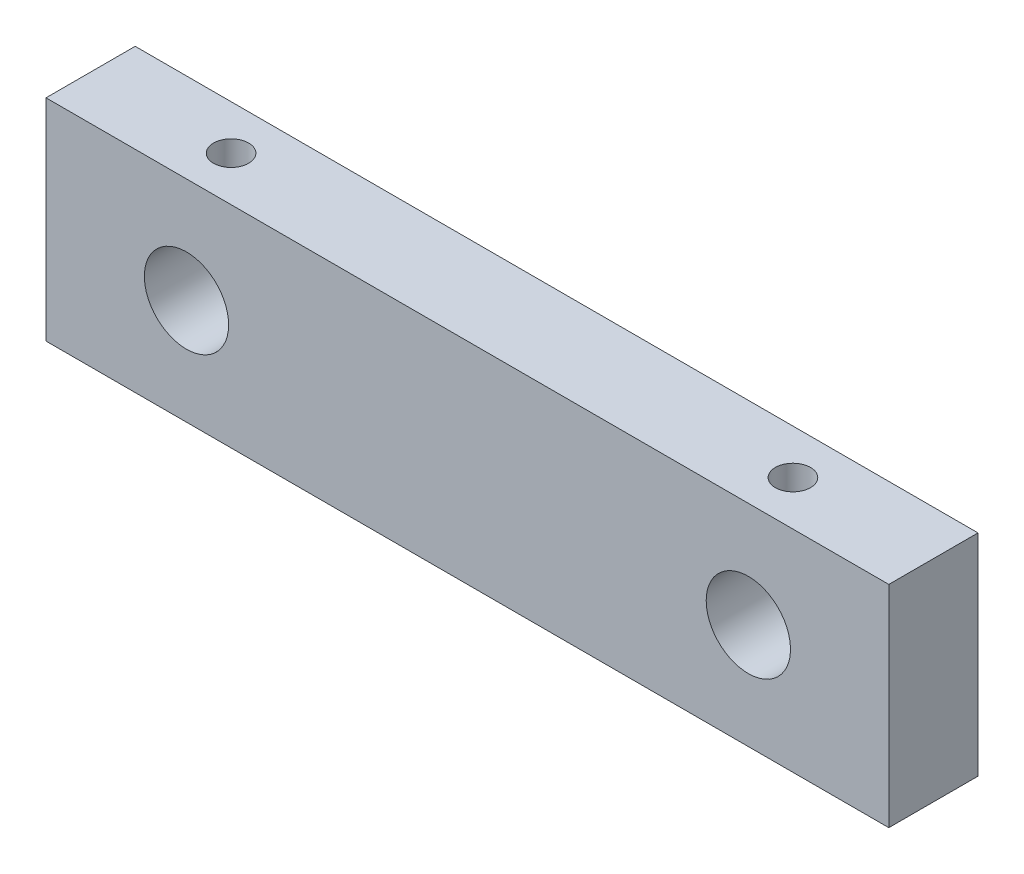
SolidWorks part; units mm, degrees
material "6061 Alloy"
ref_plane "Front Plane" through (0, 0, 0) normal (0, 0, 1) x (1, 0, 0)
ref_plane "Top Plane" through (0, 0, 0) normal (0, 1, 0) x (1, 0, 0)
ref_plane "Right Plane" through (0, 0, 0) normal (1, 0, 0) x (0, 0, -1)
sketch "Sketch1" plane through (0, 0, 0) normal (0, 0, 1) x (1, 0, 0)
  line L0 (30, 15) -> (30, 0) construction
  line L1 (0, 0) -> (60, 0)
  line L2 (0, 0) -> (0, 15)
  line L3 (0, 15) -> (60, 15)
  line L4 (60, 0) -> (60, 15)
  line L5 (0, 7.5) -> (60, 7.5) construction
  circle A0 centre (10, 7.5) radius 3
  circle A1 centre (50, 7.5) radius 3
  dimension "D3" = 6
  dimension "D1" = 60
  dimension "D2" = 15
  dimension "D4" = 40
extrude "Boss-Extrude1" add sketch "Sketch1" along normal blind 6.35
ref_axis "Axis1" through (10, 7.5, 6.35) along (0, 0, -1)
hole_wizard "M3 Tapped Hole1" positions "Sketch4" profile "Sketch3" tap size "M3" standard "ISO"
sketch "Sketch4" plane through (0, 15, 0) normal (0, 1, 0) x (-1, 0, 0)
  line L0 (0, 3.175) -> (-60, 3.175) construction
  line L1 (0, 6.35) -> (0, 0) construction
  line L2 (-60, 6.35) -> (-60, 0) construction
  line L5 (-30, 0) -> (-30, 6.35) construction
  line L6 (-60, 0) -> (0, 0) construction
  line L7 (-60, 6.35) -> (0, 6.35) construction
  line L10 (-10, 6.35) -> (-10, 0) construction
  point P0 (-10, 3.175)
  point P25 (-50, 3.175)
sketch "Sketch3" plane through (10, 15, 3.175) normal (1, 0, 0) x (0, 0, 1)
  line L0 (0, 0) -> (0, 9.2511)
  line L1 (0, 9.2511) -> (1.25, 8.5)
  line L2 (1.25, 8.5) -> (1.25, 0)
  line L5 (1.25, 0) -> (0, 0)
  line L10 (0, 9.2511) -> (-1.25, 8.5) construction
  line L11 (0, -6.35) -> (0, 107.95) construction
  dimension "Tap Drill Dia." = 2.5
  dimension "Tap Drill Depth" = 8.5
  dimension "Drill Angle" = 118
cosmetic thread "Hole Thread1" parameters "D1"=4.8642, "D2"=3
cosmetic thread "Hole Thread2" parameters "D1"=4.8642, "D2"=3
ref_plane "Plane1" through (30, 0, 0) normal (-1, 0, 0) x (0, 0, 1)
ref_plane "Belt plane" through (19, 0, 0) normal (-1, 0, 0) x (0, 0, 1)
